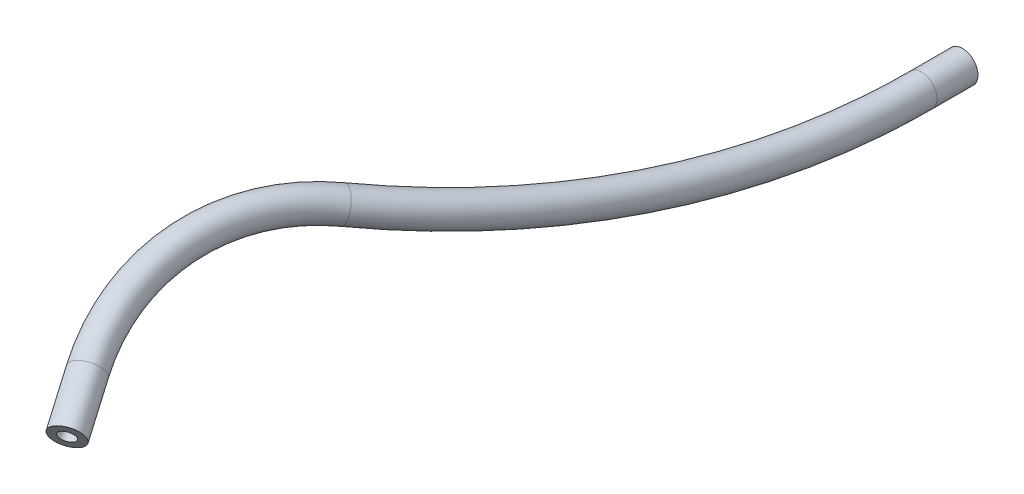
SolidWorks part; units mm, degrees
material "Silicon Rubber"
ref_plane "X-Y Datum" through (0, 0, 0) normal (0, 0, 1) x (1, 0, 0)
ref_plane "X-Z Datum" through (0, 0, 0) normal (0, 1, 0) x (1, 0, 0)
ref_plane "Y-Z Datum" through (0, 0, 0) normal (1, 0, 0) x (0, 0, -1)
sketch3d "3DSketch1"
  line L0 (-25.1447, 46.783, -16.765) -> (-25.1447, 46.783, 0)
  line L1 (-68.8755, 55.0059, 306.1658) -> (-77.7622, 65.1229, 288.925)
  circle A0 centre (-25.1447, 46.783, 0) radius 1.524 construction
  circle A1 centre (-25.1447, 46.783, 0) radius 1.524 construction
  circle A2 centre (-25.1447, 46.783, -16.765) radius 3.175 construction
  circle A3 centre (-25.1447, 46.783, -16.765) radius 3.175 construction
  circle A4 centre (-68.8755, 55.0059, 306.1658) radius 3.175 construction
  circle A5 centre (-68.8755, 55.0059, 306.1658) radius 3.175 construction
  circle A6 centre (-77.7622, 65.1229, 288.925) radius 2.5758 construction
  circle A7 centre (-77.7622, 65.1229, 288.925) radius 2.5758 construction
  arc A8 (-25.1447, 46.783, 0) -> (-73.6743, 76.0968, 188.4747) centre (-317.5609, 223.4144, 0) ccw
  arc A9 (-77.7622, 65.1229, 288.925) -> (-73.6743, 76.0968, 188.4747) centre (-21.2927, 24.2848, 235.8539) ccw
  point P2 (-25.1447, 46.783, 1.524)
  point P4 (-25.1447, 46.783, 1.524)
  point P7 (-25.1447, 46.783, -19.94)
  point P9 (-25.1447, 46.783, -19.94)
  point P12 (-70.1653, 56.4742, 303.6636)
  point P14 (-70.1653, 56.4742, 303.6636)
  point P17 (-78.8086, 66.3142, 286.895)
  point P19 (-78.8086, 66.3142, 286.895)
  point P21 (-494.1923, -69.0019, 0)
  point P26 (-78.021, -41.7778, 226.3282)
  dimension "D1" = 341.6224
sweep "Sweep1" add path "3DSketch1" circular profile diameter 12.7 parameters "D3"=12.7
sweep "Cut-Sweep1" cut path "3DSketch1<2>" circular profile diameter 6.35 parameters "D3"=6.35
sketch3d "3DSketch1<2>" same geometry as "3DSketch1"
